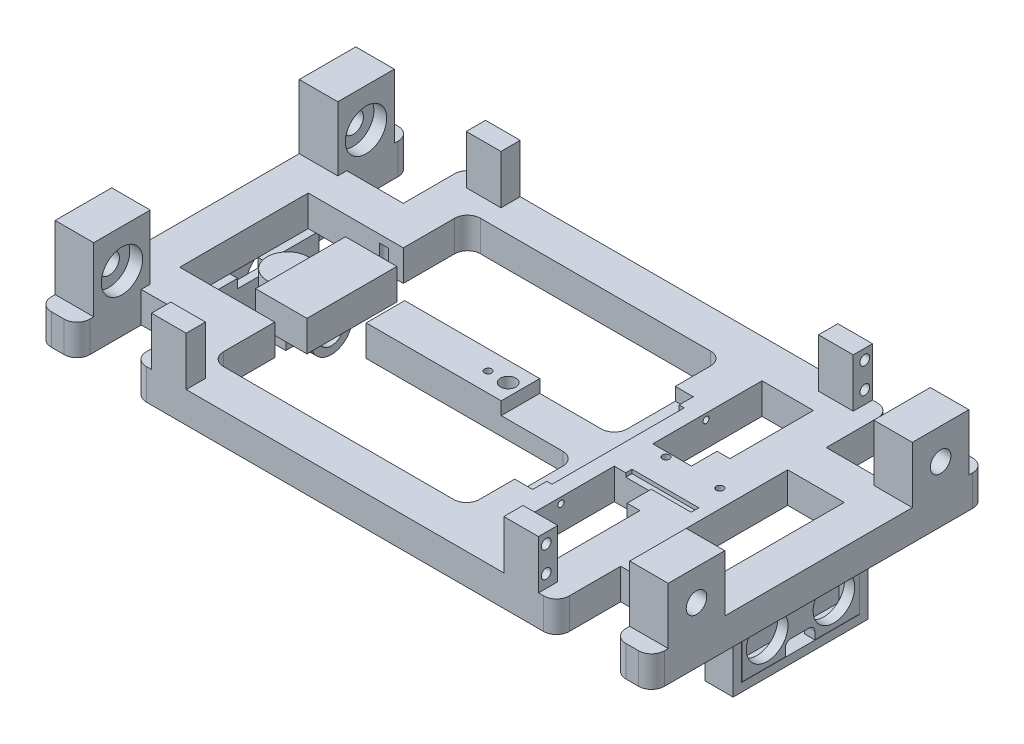
SolidWorks part; units mm, degrees
note: The reader was unsure of these and kept them because the rebuilt part matched: shared geometry of "Sketch42<4>", "Sketch103<3>".
other "DogBody"
other "frontCover"
ref_plane "Front Plane" through (0, 0, 0) normal (0, 0, 1) x (1, 0, 0)
ref_plane "Top Plane" through (0, 0, 0) normal (0, 1, 0) x (1, 0, 0)
ref_plane "Right Plane" through (0, 0, 0) normal (1, 0, 0) x (0, 0, -1)
sketch "Sketch1" plane through (0, 0, 0) normal (0, 1, 0) x (1, 0, 0)
  line L0 (-104.3, -65) -> (-104.3, -7.5)
  line L1 (-119.3, -65) -> (-104.3, -65)
  line L2 (-119.3, -65) -> (-119.3, 65)
  line L3 (-119.3, 65) -> (-104.3, 65)
  line L4 (119.3, -65) -> (119.3, 65)
  line L5 (104.3, 65) -> (104.3, 7.5)
  line L6 (-82.3, -65) -> (-82.3, -7.5)
  line L7 (-67.3, -50) -> (-67.3, -17.5)
  line L8 (82.3, -65) -> (82.3, -7.5)
  line L9 (67.3, -50) -> (67.3, -17.5)
  line L10 (-119.3, 0) -> (119.3, 0) construction
  line L11 (-104.3, -7.5) -> (-82.3, -7.5)
  line L12 (-104.3, 7.5) -> (-82.3, 7.5)
  line L13 (-63.3, -7.5) -> (-63.3, -17.5)
  line L14 (-67.3, 17.5) -> (-63.3, 17.5)
  line L15 (-67.3, 50) -> (67.3, 50)
  line L16 (-82.3, 65) -> (82.3, 65)
  line L18 (104.3, 65) -> (119.3, 65)
  line L19 (104.3, -65) -> (119.3, -65)
  line L20 (-67.3, -17.5) -> (-63.3, -17.5)
  line L21 (-82.3, -65) -> (82.3, -65)
  line L22 (-67.3, -50) -> (67.3, -50)
  line L23 (-104.3, 7.5) -> (-104.3, 65)
  line L24 (-82.3, 7.5) -> (-82.3, 65)
  line L25 (-67.3, 17.5) -> (-67.3, 50)
  line L26 (67.3, 17.5) -> (67.3, 50)
  line L27 (82.3, 7.5) -> (82.3, 65)
  line L28 (104.3, -7.5) -> (104.3, -65)
  line L29 (-119.3, 7.5) -> (119.3, 7.5) construction
  line L30 (-119.3, -7.5) -> (119.3, -7.5) construction
  line L31 (82.3, -7.5) -> (104.3, -7.5)
  line L32 (82.3, 7.5) -> (104.3, 7.5)
  line L33 (-63.3, -7.5) -> (63.3, -7.5)
  line L34 (-63.3, 7.5) -> (63.3, 7.5)
  line L35 (-104.3, 65) -> (-82.3, 65) construction
  line L36 (82.3, 65) -> (104.3, 65) construction
  line L37 (82.3, -65) -> (104.3, -65) construction
  line L38 (-82.3, -65) -> (-104.3, -65) construction
  line L39 (-63.3, 17.5) -> (-63.3, 7.5)
  line L40 (0, -1000) -> (0, 49000) construction
  line L41 (63.3, -7.5) -> (63.3, -17.5)
  line L42 (67.3, -17.5) -> (63.3, -17.5)
  line L43 (67.3, 17.5) -> (63.3, 17.5)
  line L44 (63.3, 17.5) -> (63.3, 7.5)
  dimension "D1" = 65
  dimension "D2" = 130
  dimension "D3" = 15
  dimension "D4" = 22
  dimension "D5" = 15
  dimension "D6" = 15
  dimension "D7" = 22
  dimension "D11" = 15
  dimension "D12" = 15
  dimension "D13" = 238.6
  dimension "D14" = 119.3
  dimension "D15" = 10
  dimension "D16" = 4
  dimension "D17" = 10
  dimension "D9" = 7.5
  dimension "D10" = 7.5
extrude "Boss-Extrude1" add sketch "Sketch1" along normal blind 12
sketch "Sketch2" plane through (0, 12, 0) normal (0, 1, 0) x (1, 0, 0)
  line L0 (-82.3, 65) -> (-82.3, 7.5) construction
  line L1 (-75.3, 57.5) -> (-63.3, 57.5)
  line L2 (-75.3, 57.5) -> (-75.3, 65)
  line L3 (-75.3, 65) -> (-63.3, 65)
  line L4 (-63.3, 57.5) -> (-63.3, 65)
  line L5 (82.3, 65) -> (-82.3, 65) construction
  line L6 (-75.3, 57) -> (-63.3, 57) construction
  line L7 (-112.3144, 32.5) -> (114.0355, 32.5) construction
  line L8 (0, 0) -> (0, 64.2149) construction
  line L14 (0, 0) -> (-63.3, 0) construction
  line L15 (-75.3, -57) -> (-63.3, -57) construction
  line L16 (-75.3, -65) -> (-63.3, -65)
  line L17 (-63.3, -57.5) -> (-63.3, -65)
  line L18 (-75.3, -57.5) -> (-63.3, -57.5)
  line L19 (-75.3, -57.5) -> (-75.3, -65)
  line L22 (-63.3, -7.5) -> (-63.3, 0)
  line L23 (-63.3, 0) -> (-63.3, 7.5)
  line L24 (-75.3, 7.5) -> (-75.3, 0)
  line L25 (-75.3, 0) -> (-75.3, -7.5)
  line L26 (75.3, -57) -> (63.3, -57) construction
  line L27 (75.3, -57.5) -> (75.3, -65)
  line L28 (75.3, -57.5) -> (63.3, -57.5)
  line L29 (63.3, -57.5) -> (63.3, -65)
  line L30 (75.3, -65) -> (63.3, -65)
  line L31 (-75.3, 0) -> (-136.6898, 0) construction
  line L33 (75.3, 7.5) -> (75.3, 0)
  line L35 (63.3, 0) -> (63.3, 7.5)
  line L36 (63.3, -7.5) -> (63.3, 0)
  line L38 (75.3, 0) -> (75.3, -7.5)
  line L39 (75.3, 57) -> (63.3, 57) construction
  line L40 (75.3, 65) -> (63.3, 65)
  line L41 (63.3, 57.5) -> (63.3, 65)
  line L42 (75.3, 57.5) -> (63.3, 57.5)
  line L43 (75.3, 57.5) -> (75.3, 65)
  line L50 (75.3, -7.5) -> (75.3, -17.5)
  line L51 (75.3, -17.5) -> (63.3, -17.5)
  line L52 (63.3, -7.5) -> (63.3, -17.5)
  line L54 (-75.3, 7.5) -> (-75.3, 17.5)
  line L55 (-75.3, 17.5) -> (-63.3, 17.5)
  line L56 (-63.3, 7.5) -> (-63.3, 17.5)
  line L58 (-63.3, -7.5) -> (-63.3, -17.5)
  line L59 (-63.3, -17.5) -> (-75.3, -17.5)
  line L60 (-75.3, -7.5) -> (-75.3, -17.5)
  line L61 (63.3, 7.5) -> (63.3, 17.5)
  line L62 (63.3, 17.5) -> (75.3, 17.5)
  line L63 (75.3, 7.5) -> (75.3, 17.5)
  point P29 (-63.3, 0)
  point P32 (-75.3, 0)
  dimension "D1" = 7
  dimension "D2" = 7.5
  dimension "D3" = 12
  dimension "D4" = 10
  dimension "D5" = 24.5
  dimension "D6" = 10
  dimension "D7" = 10
  dimension "D8" = 10
extrude "Boss-Extrude2" add sketch "Sketch2" along normal blind 19
sketch "Sketch3" plane through (-75.3, 0, 0) normal (-1, 0, 0) x (0, 0, 1)
  line L0 (-37.5, -10.7851) -> (-37.5, 36.9377) construction
  line L1 (-57.5, 31) -> (-57.5, 12) construction
  line L2 (-65, 12) -> (65, 12) construction
  line L3 (0, 0) -> (0, 40.8102) construction
  line L4 (-65, 0) -> (65, 0) construction
  circle A0 centre (-62, 17) radius 1.9
  circle A1 centre (-62, 27) radius 1.9
  circle A2 centre (-13, 17) radius 1.9
  circle A3 centre (-13, 27) radius 1.9
  circle A4 centre (13, 27) radius 1.9
  circle A5 centre (13, 17) radius 1.9
  circle A6 centre (62, 17) radius 1.9
  circle A7 centre (62, 27) radius 1.9
  dimension "D3" = 3.8
  dimension "D4" = 3.8
  dimension "D1" = 4.5
  dimension "D2" = 4.5
  dimension "D5" = 10
  dimension "D6" = 5
  dimension "D7" = 24.5
extrude "Cut-Extrude1" cut sketch "Sketch3" against normal through all
sketch "Sketch4" plane through (104.3, 0, 0) normal (-1, 0, 0) x (0, 0, 1)
  line L0 (57.5, 31) -> (57.5, 12) construction
  line L1 (-65, 12) -> (65, 12) construction
  line L2 (-1000, 0) -> (49000, 0) construction
  line L3 (0, -1000) -> (0, 49000) construction
  line L4 (65, 31) -> (65, 12) construction
  line L5 (-58.5, 12) -> (-36.5, 12)
  line L6 (-58.5, 12) -> (-58.5, 34)
  line L7 (-58.5, 34) -> (-36.5, 34)
  line L8 (-36.5, 12) -> (-36.5, 34)
  line L9 (58.5, 12) -> (36.5, 12)
  line L10 (58.5, 12) -> (58.5, 34)
  line L11 (58.5, 34) -> (36.5, 34)
  line L12 (36.5, 12) -> (36.5, 34)
  line L13 (-65, 31) -> (-65, 12) construction
  circle A0 centre (47.5, 22) radius 8.05
  circle A1 centre (-47.5, 22) radius 8.05
  dimension "D1" = 16.1
  dimension "D2" = 10
  dimension "D3" = 10
  dimension "D4" = 22
  dimension "D5" = 22
  dimension "D6" = 22
  dimension "D7" = 22
  dimension "D8" = 6.5
  dimension "D9" = 6.5
extrude "Boss-Extrude3" add sketch "Sketch4" against normal blind 5 separate body
sketch "Sketch6" plane through (109.3, 0, 0) normal (1, 0, 0) x (0, 0, -1)
  line L5 (-58.5, 12) -> (-36.5, 12)
  line L10 (58.5, 12) -> (36.5, 12)
  line L11 (58.5, 12) -> (58.5, 34)
  line L12 (58.5, 34) -> (36.5, 34)
  line L13 (36.5, 12) -> (36.5, 34)
  line L14 (-58.5, 12) -> (-58.5, 34)
  line L15 (-58.5, 34) -> (-36.5, 34)
  line L16 (-36.5, 12) -> (-36.5, 34)
  circle A0 centre (-47.5, 22) radius 4
  circle A1 centre (47.5, 22) radius 4
  dimension "D1" = 8
  dimension "D2" = 8
extrude "Boss-Extrude4" add sketch "Sketch6" along normal blind 6
mirror "Mirror1" about plane through (0, 0, 0) normal (1, 0, 0) of bodies 228 106 107
sketch "Sketch7" plane through (0, 0, 0) normal (0, 1, 0) x (1, 0, 0)
  line L0 (-104.3, 36.5) -> (-104.3, 58.5) construction
  line L1 (-104.3, 40) -> (-82.3, 40)
  line L2 (-104.3, 40) -> (-104.3, 25)
  line L4 (-82.3, 40) -> (-82.3, 25)
  line L5 (-75.3, 57.5) -> (-63.3, 57.5) construction
  line L7 (-104.3, 25) -> (-82.3, 25)
  line L9 (-1000, 0) -> (49000, 0) construction
  line L10 (0, -1000) -> (0, 49000) construction
  line L11 (104.3, 40) -> (104.3, 25)
  line L12 (104.3, 25) -> (82.3, 25)
  line L13 (82.3, 40) -> (82.3, 25)
  line L14 (104.3, 40) -> (82.3, 40)
  line L15 (104.3, -40) -> (82.3, -40)
  line L16 (82.3, -40) -> (82.3, -25)
  line L17 (104.3, -25) -> (82.3, -25)
  line L18 (104.3, -40) -> (104.3, -25)
  line L19 (-104.3, -40) -> (-104.3, -25)
  line L20 (-104.3, -25) -> (-82.3, -25)
  line L21 (-82.3, -40) -> (-82.3, -25)
  line L22 (-104.3, -40) -> (-82.3, -40)
  dimension "D1" = 17.5
  dimension "D2" = 15
  dimension "D3" = 22
extrude "Boss-Extrude5" add sketch "Sketch7" along normal blind 12
sketch "Sketch8" plane through (0, 12, 0) normal (0, 1, 0) x (1, 0, 0)
  line L1 (-104.3, 25) -> (-82.3, 25)
  line L2 (-104.3, 25) -> (-104.3, -25)
  line L3 (-104.3, -25) -> (-82.3, -25)
  line L4 (-82.3, 25) -> (-82.3, -25)
  line L5 (82.3, -25) -> (104.3, -25)
  line L6 (82.3, -25) -> (82.3, 25)
  line L7 (82.3, 25) -> (104.3, 25)
  line L8 (104.3, -25) -> (104.3, 25)
extrude "Cut-Extrude2" cut sketch "Sketch8" against normal through all
sketch "Sketch14" plane through (0, 0, 0) normal (0, 1, 0) x (1, 0, 0)
  line L0 (-67.3, -50) -> (67.3, -50) construction
  line L1 (-7.5, -50) -> (7.5, -50)
  line L2 (-7.5, -50) -> (-7.5, -7.5)
  line L3 (-7.5, 50) -> (7.5, 50)
  line L4 (7.5, -50) -> (7.5, -7.5)
  line L5 (67.3, 50) -> (-67.3, 50) construction
  line L6 (63.3, -7.5) -> (-63.3, -7.5) construction
  line L7 (-63.3, 7.5) -> (63.3, 7.5) construction
  line L8 (7.5, -7.5) -> (-7.5, -7.5)
  line L9 (-7.5, 7.5) -> (7.5, 7.5)
  line L10 (7.5, 7.5) -> (7.5, 50)
  line L11 (-7.5, 7.5) -> (-7.5, 50)
  dimension "D1" = 15
  dimension "D2" = 7.5
extrude "Boss-Extrude8" add sketch "Sketch14" along normal up to surface (12 mm away) up to face at (0, 12, 0)
sketch "Sketch15" plane through (0, 12, 0) normal (0, 1, 0) x (1, 0, 0)
  line L1 (3.3, -31.25) -> (39.3, -31.25)
  line L2 (3.3, -31.25) -> (3.3, 31.25)
  line L4 (39.3, -31.25) -> (39.3, 31.25)
  line L5 (75.3, 57.5) -> (75.3, 65) construction
  line L8 (3.3, 31.25) -> (39.3, 31.25)
  line L9 (-47.3, 14) -> (0.7, 14)
  line L10 (-47.3, 14) -> (-47.3, -14)
  line L11 (-47.3, -14) -> (0.7, -14)
  line L12 (0.7, 14) -> (0.7, -14)
  line L13 (3.3, 27.75) -> (39.3, 27.75) construction
  line L14 (3.3, -27.75) -> (39.3, -27.75) construction
  line L15 (-75.3, 65) -> (-75.3, 57.5) construction
  line L16 (-39.3, -998.765) -> (-39.3, 49001.235) construction
  line L17 (39.3, -1009.0627) -> (39.3, 48990.9373) construction
  point P17 (-75.3, 61.25)
  dimension "D1" = 36
  dimension "D2" = 36
  dimension "D3" = 48
  dimension "D4" = 28
  dimension "D5" = 31.25
  dimension "D6" = 62.5
  dimension "D7" = 55.5
  dimension "D8" = 3.5
  dimension "D9" = 28
  dimension "D10" = 14
  dimension "D11" = 2.6
sketch "Sketch16" plane through (0, 12, 0) normal (0, 1, 0) x (1, 0, 0)
  line L1 (-7.5, 50) -> (7.5, 50)
  line L2 (-7.5, 50) -> (-7.5, 7.5)
  line L3 (-7.5, 7.5) -> (7.5, 7.5)
  line L4 (7.5, 50) -> (7.5, 7.5)
  line L5 (-7.5, -7.5) -> (7.5, -7.5)
  line L6 (-7.5, -7.5) -> (-7.5, -50)
  line L7 (-7.5, -50) -> (7.5, -50)
  line L8 (7.5, -7.5) -> (7.5, -50)
extrude "Cut-Extrude8" cut sketch "Sketch16" against normal through all
sketch "Sketch17" plane through (0, 0, 0) normal (0, 1, 0) x (1, 0, 0)
  line L0 (67.3, 50) -> (-67.3, 50) construction
  line L1 (32.3, 50) -> (47.3, 50)
  line L2 (32.3, 50) -> (32.3, 7.5)
  line L3 (32.3, 7.5) -> (47.3, 7.5)
  line L4 (47.3, 50) -> (47.3, 7.5)
  line L5 (-63.3, 7.5) -> (63.3, 7.5) construction
  line L6 (63.3, -7.5) -> (-63.3, -7.5) construction
  line L7 (32.3, -7.5) -> (47.3, -7.5)
  line L8 (32.3, -7.5) -> (32.3, -50)
  line L9 (32.3, -50) -> (47.3, -50)
  line L10 (47.3, -7.5) -> (47.3, -50)
  line L11 (-67.3, -50) -> (67.3, -50) construction
  line L12 (39.3, -201009.0627) -> (39.3, 248990.9373) construction
  dimension "D1" = 15
  dimension "D2" = 15
  dimension "D3" = 7
  dimension "D4" = 7
extrude "Boss-Extrude9" add sketch "Sketch17" along normal up to surface (12 mm away) up to face at (-93.3, 12, 0)
extrude "Cut-Extrude9" cut sketch "Sketch15" against normal blind 5 contours L8 L2 L1 L4
sketch "Sketch18" plane through (39.3, 0, 0) normal (-1, 0, 0) x (0, 0, 1)
  line L0 (31.25, 7) -> (-31.25, 7) construction
  line L1 (-31.25, 12) -> (-31.25, 7) construction
  line L2 (31.25, 12) -> (31.25, 7) construction
  circle A0 centre (28.25, 9.7) radius 1.2
  circle A1 centre (-28.25, 9.7) radius 1.2
  dimension "D1" = 2.4
  dimension "D2" = 2.4
  dimension "D3" = 2.7
  dimension "D4" = 2.7
  dimension "D5" = 3
  dimension "D6" = 3
extrude "Cut-Extrude10" cut sketch "Sketch18" against normal up to next
sketch "Sketch19" plane through (39.3, 0, 0) normal (-1, 0, 0) x (0, 0, 1)
  line L0 (-31.25, 7) -> (-7.5, 7) construction
  line L1 (-25.75, 7) -> (25.75, 7)
  line L2 (-25.75, 7) -> (-25.75, 14)
  line L3 (-25.75, 14) -> (25.75, 14)
  line L4 (25.75, 7) -> (25.75, 14)
  dimension "D1" = 7
  dimension "D2" = 51.5
  dimension "D3" = 25.75
extrude "Cut-Extrude11" cut sketch "Sketch19" against normal blind 2
sketch "Sketch41" plane through (0, 0, 0) normal (0, -1, 0) x (1, 0, 0)
  line L5 (119.3, 65) -> (119.3, -65) construction
  line L8 (104.3, 22.75) -> (104.3, -22.75) construction
  line L24 (104.3, -22.75) -> (101.3, -22.75)
  line L25 (104.3, -22.75) -> (104.3, 22.75)
  line L26 (104.3, 22.75) -> (101.3, 22.75)
  line L27 (101.3, -22.75) -> (101.3, 22.75)
  line L28 (101.3, 22.75) -> (104.3, 22.75)
  line L29 (101.3, 22.75) -> (101.3, 26.25)
  line L30 (101.3, 26.25) -> (104.3, 26.25)
  line L31 (104.3, 22.75) -> (104.3, 26.25)
  line L32 (101.3, -22.75) -> (104.3, -22.75)
  line L33 (101.3, -22.75) -> (101.3, -26.25)
  line L34 (101.3, -26.25) -> (104.3, -26.25)
  line L35 (104.3, -22.75) -> (104.3, -26.25)
  dimension "D1" = 15
  dimension "D7" = 3.5
  dimension "D8" = 3.5
  dimension "D9" = 3
extrude "Boss-Extrude18" add sketch "Sketch41" along normal blind 24 separate body
sketch "Sketch42" plane through (104.3, 0, 0) normal (1, 0, 0) x (0, 0, -1)
  line L1 (-26.25, 0) -> (26.25, 0)
  line L2 (-26.25, 0) -> (-26.25, -24)
  line L3 (-26.25, -24) -> (26.25, -24)
  line L4 (26.25, 0) -> (26.25, -24)
  line L5 (-22.95, 0) -> (22.95, 0)
  line L6 (-22.95, 0) -> (-22.95, -20.7)
  line L7 (-22.95, -20.7) -> (22.95, -20.7)
  line L8 (22.95, 0) -> (22.95, -20.7)
  line L9 (-5.5, -5.0608) -> (5.5, -5.0608) construction
  line L10 (-5.5, -5.0608) -> (-5.5, 3.3558) construction
  line L11 (-5.5, 3.3558) -> (5.5, 3.3558) construction
  line L12 (5.5, -5.0608) -> (5.5, 3.3558) construction
  line L13 (-5.5, -3.3) -> (-19.95, -3.3)
  line L14 (-5.5, -3.3) -> (-5.5, 0)
  line L15 (-5.5, 0) -> (-19.95, 0)
  line L16 (-19.95, -3.3) -> (-19.95, 0)
  line L17 (5.5, -3.3) -> (19.95, -3.3)
  line L18 (5.5, -3.3) -> (5.5, 0)
  line L19 (5.5, 0) -> (19.95, 0)
  line L20 (19.95, -3.3) -> (19.95, 0)
  line L21 (5.5, -3.5) -> (-5.5, -3.5)
  line L22 (5.5, -3.5) -> (5.5, 0)
  line L23 (5.5, 0) -> (-5.5, 0)
  line L24 (-5.5, -3.5) -> (-5.5, 0)
  line M8 (26.25, 0) -> (-26.25, 0)
  line M9 (-26.25, 0) -> (-26.25, -24)
  line M10 (-26.25, -24) -> (26.25, -24)
  line M11 (26.25, -24) -> (26.25, 0)
  dimension "D1" = 3.3
  dimension "D2" = 3.3
  dimension "D3" = 3.3
  dimension "D4" = 11
  dimension "D5" = 5.5
  dimension "D6" = 3.3
  dimension "D7" = 3.3
  dimension "D8" = 3
  dimension "D9" = 3
  dimension "D10" = 3.5
extrude "Boss-Extrude19" add sketch "Sketch42" along normal blind 8 contours L8 L7 L6 M8 M9 M10 M11
sketch "Sketch48" plane through (104.3, 0, 0) normal (1, 0, 0) x (0, 0, -1)
  line L0 (-13, -10.5) -> (13, -10.5) construction
  line L1 (-5.25, -2.5) -> (-5.25, -0.1)
  line L2 (-22.95, -20.7) -> (22.95, -20.7) construction
  line L3 (-5.95, -17.7) -> (-5.95, -20.6)
  line L4 (-3.75, -17.7) -> (3.35, -17.7) construction
  line L5 (-3.75, -15.5) -> (3.35, -15.5)
  line L7 (5.55, -17.7) -> (5.55, -20.6)
  line L8 (-22.95, -20.7) -> (22.95, -20.7) construction
  line L9 (-3.75, -2.5) -> (3.7505, -2.5) construction
  line L11 (-3.75, -4) -> (3.7505, -4)
  line L12 (-65, 0) -> (65, 0) construction
  line L13 (-22.95, 0) -> (-22.95, -20.7) construction
  line L14 (-22.85, -20.6) -> (-5.95, -20.6)
  line L15 (-22.85, -20.6) -> (-22.85, -0.1)
  line L16 (-22.85, -0.1) -> (-5.25, -0.1)
  line L17 (22.85, -20.6) -> (22.85, -0.1)
  line L18 (22.95, 0) -> (22.95, -20.7) construction
  line L19 (5.55, -20.6) -> (22.85, -20.6)
  line L20 (5.25, -2.4627) -> (5.25, -0.1)
  line L21 (5.25, -0.1) -> (22.85, -0.1)
  circle A0 centre (-13, -10.5) radius 8.1
  circle A1 centre (13, -10.5) radius 8.1
  arc A2 (-3.75, -15.5) -> (-5.95, -17.7) centre (-3.75, -17.7) ccw
  arc A3 (5.55, -17.7) -> (3.35, -15.5) centre (3.35, -17.7) ccw
  arc A5 (-5.25, -2.5) -> (-3.75, -4) centre (-3.75, -2.5) ccw
  arc A6 (3.7505, -4) -> (5.25, -2.4627) centre (3.7505, -2.5) ccw
  point P13 (0, -17.7)
  point P23 (0, -2.5)
  dimension "D1" = 16.2
  dimension "D2" = 16.2
  dimension "D6" = 2.2
  dimension "D7" = 11.5
  dimension "D10" = 1.5
  dimension "D12" = 5.25
  dimension "D8" = 2.2
  dimension "D11" = 1.5
  dimension "D19" = 5.1
  dimension "D22" = 5.55
  dimension "D3" = 26
  dimension "D4" = 13
  dimension "D5" = 10.2
  dimension "D9" = 10.5
  dimension "D13" = 3.9
  dimension "D14" = 0.1
  dimension "D15" = 0.1
  dimension "D16" = 0.1
  dimension "D17" = 0.1
  dimension "D18" = 7.5005
  dimension "D20" = 2.4
  dimension "D21" = 2.9
extrude "Boss-Extrude22" add sketch "Sketch48" along normal blind 4 from offset 5 separate body
sketch "Sketch55" plane through (0, 12, 0) normal (0, 1, 0) x (1, 0, 0)
  line L0 (63.3, 65) -> (-63.3, 65) construction
  line L1 (-63.3, 57.5) -> (-61.8, 57.5)
  line L2 (-63.3, 57.5) -> (-63.3, 65)
  line L3 (-63.3, 65) -> (-61.8, 65)
  line L4 (-61.8, 57.5) -> (-61.8, 65)
  line L6 (63.3, 57.5) -> (61.8, 57.5)
  line L7 (63.3, 57.5) -> (63.3, 65)
  line L8 (63.3, 65) -> (61.8, 65)
  line L9 (61.8, 57.5) -> (61.8, 65)
  line L19 (-63.3, -65) -> (63.3, -65) construction
  line L20 (63.3, -57.5) -> (61.8, -57.5)
  line L21 (63.3, -57.5) -> (63.3, -65)
  line L22 (63.3, -65) -> (61.8, -65)
  line L23 (61.8, -57.5) -> (61.8, -65)
  line L25 (-63.3, -57.5) -> (-61.8, -57.5)
  line L26 (-63.3, -57.5) -> (-63.3, -65)
  line L27 (-63.3, -65) -> (-61.8, -65)
  line L28 (-61.8, -57.5) -> (-61.8, -65)
  dimension "D2" = 1.5
  dimension "D3" = 1.5
  dimension "D5" = 1.5
  dimension "D6" = 1.5
extrude "Boss-Extrude27" add sketch "Sketch55" along normal up to surface (19 mm away) up to face at (-69.3, 31, 0)
extrude "Cut-Extrude27" cut sketch "Sketch42<4>" against normal up to next (3 mm away) contours L24 L21 L22 L18 L5 L14
sketch "Sketch42<4>" plane through (104.3, 0, 0) normal (1, 0, 0) x (0, 0, -1) same geometry as "Sketch42"
move or copy body "Body-Move/Copy1" bodies to move or copy 172 copy no translate (-1, 0, 0) parameters "D1"=1, "D2"=0, "D3"=0
sketch "Sketch60" plane through (0, 34, 0) normal (0, 1, 0) x (1, 0, 0)
  line L0 (-104.3, 36.5) -> (-104.3, 58.5) construction
  line L1 (-104.3, 58.5) -> (-115.3, 58.5) construction
  line L2 (-115.3, 58.5) -> (-115.3, 36.5) construction
  line L3 (-115.3, 36.5) -> (-104.3, 36.5) construction
  line L4 (-104.3, -58.5) -> (-104.3, -36.5) construction
  line L5 (-104.3, -36.5) -> (-115.3, -36.5) construction
  line L7 (-115.3, -58.5) -> (-104.3, -58.5) construction
  line L8 (-104.3, 36.5) -> (-104.3, 58.5)
  line L9 (-104.3, 58.5) -> (-115.3, 58.5)
  line L10 (-115.3, 58.5) -> (-115.3, 36.5)
  line L11 (-115.3, 36.5) -> (-104.3, 36.5)
  line L12 (-104.3, -58.5) -> (-104.3, -36.5)
  line L13 (-104.3, -36.5) -> (-115.3, -36.5)
  line L14 (-115.3, -36.5) -> (-115.3, -58.5)
  line L15 (-115.3, -58.5) -> (-104.3, -58.5)
extrude "Boss-Extrude28" add sketch "Sketch60" along normal blind 3
sketch "Sketch62" plane through (0, 0, 0) normal (0, -1, 0) x (1, 0, 0)
  line L0 (0, -1000) -> (0, 49000) construction
  line L2 (-67.3, 17.5) -> (-67.3, 50) construction
  line L4 (-67.3, -50) -> (-67.3, -17.5) construction
  line L6 (82.3, -65) -> (-82.3, -65) construction
  line L7 (-82.3, 65) -> (82.3, 65) construction
  line L8 (32.3, -50) -> (-67.3, -50) construction
  circle A0 centre (-74.8, 25) radius 1.825
  circle A1 centre (-74.8, -25) radius 1.825
  circle A2 centre (-74.8, -57.5) radius 1.825
  circle A3 centre (-74.8, 57.5) radius 1.825
  circle A4 centre (0, 57.5) radius 1.825
  circle A5 centre (0, -57.5) radius 1.825
  circle A6 centre (74.8, -57.5) radius 1.825
  circle A7 centre (74.8, -25) radius 1.825
  circle A8 centre (74.8, 25) radius 1.825
  circle A9 centre (74.8, 57.5) radius 1.825
  dimension "D3" = 3.65
  dimension "D4" = 3.65
  dimension "D9" = 3.65
  dimension "D10" = 3.65
  dimension "D12" = 7.5
  dimension "D14" = 3.65
  dimension "D15" = 3.65
  dimension "D1" = 25
  dimension "D2" = 25
  dimension "D5" = 7.5
  dimension "D6" = 7.5
  dimension "D7" = 7.5
  dimension "D8" = 7.5
  dimension "D11" = 7.5
  dimension "D13" = 7.5
  dimension "D16" = 7.5
extrude "Cut-Extrude33" cut sketch "Sketch62" against normal blind 9
fillet "Fillet4" radius 5 18 edges at (-119.3, 6, -65) (-104.3, 6, -65) (-82.3, 6, -65) (-119.3, 6, 65) (-104.3, 6, 65) (-82.3, 6, 65) (119.3, 6, -65) (104.3, 6, -65) (82.3, 6, -65) (119.3, 6, 65) (104.3, 6, 65) (82.3, 6, 65) (32.3, 3.5, -7.5) (-67.3, 6, 50) (32.3, 6, 50) (32.3, 3.5, 7.5) (-67.3, 6, -50) (32.3, 6, -50) tangent propagation no
sketch "Sketch65" plane through (115.3, 0, 0) normal (1, 0, 0) x (0, 0, -1)
  line L4 (-58.5, 34) -> (-58.5, 12)
  line L5 (-58.5, 12) -> (-36.5, 12)
  line L6 (-36.5, 12) -> (-36.5, 34)
  line L7 (-36.5, 34) -> (-58.5, 34)
  line L8 (-58.5, 34) -> (-58.5, 12)
  line L9 (-58.5, 12) -> (-36.5, 12)
  line L10 (-36.5, 12) -> (-36.5, 34)
  line L11 (-36.5, 34) -> (-58.5, 34)
  line L12 (58.5, 12) -> (58.5, 34)
  line L13 (58.5, 34) -> (36.5, 34)
  line L14 (36.5, 34) -> (36.5, 12)
  line L15 (36.5, 12) -> (58.5, 12)
  line L16 (58.5, 12) -> (58.5, 34)
  line L17 (58.5, 34) -> (36.5, 34)
  line L18 (36.5, 34) -> (36.5, 12)
  line L19 (36.5, 12) -> (58.5, 12)
  circle A0 centre (-47.5, 22) radius 4 construction
  circle A1 centre (-47.5, 22) radius 4
  circle A2 centre (47.5, 22) radius 4 construction
  circle A3 centre (47.5, 22) radius 4
  dimension "D1" = 0
  dimension "D2" = 0
extrude "Boss-Extrude29" add sketch "Sketch65" along normal up to surface (4 mm away) up to face at (119.3, 6, 0)
sketch "Sketch66" plane through (-115.3, 0, 0) normal (-1, 0, 0) x (0, 0, 1)
  line L4 (-58.5, 37) -> (-58.5, 12)
  line L5 (-58.5, 12) -> (-36.5, 12)
  line L6 (-36.5, 12) -> (-36.5, 37)
  line L7 (-36.5, 37) -> (-58.5, 37)
  line L8 (-58.5, 37) -> (-58.5, 12)
  line L9 (-58.5, 12) -> (-36.5, 12)
  line L10 (-36.5, 12) -> (-36.5, 37)
  line L11 (-36.5, 37) -> (-58.5, 37)
  line L12 (58.5, 12) -> (58.5, 37)
  line L13 (58.5, 37) -> (36.5, 37)
  line L14 (36.5, 37) -> (36.5, 12)
  line L15 (36.5, 12) -> (58.5, 12)
  line L16 (58.5, 12) -> (58.5, 37)
  line L17 (58.5, 37) -> (36.5, 37)
  line L18 (36.5, 37) -> (36.5, 12)
  line L19 (36.5, 12) -> (58.5, 12)
  circle A0 centre (-47.5, 22) radius 4 construction
  circle A1 centre (-47.5, 22) radius 4
  circle A2 centre (47.5, 22) radius 4 construction
  circle A3 centre (47.5, 22) radius 4
  dimension "D1" = 0
  dimension "D2" = 0
extrude "Boss-Extrude30" add sketch "Sketch66" along normal up to surface (4 mm away) up to face at (-119.3, 6, 0)
sketch "Sketch68" plane through (-63.3, 0, 0) normal (1, 0, 0) x (0, 0, -1)
  line L8 (-17.5, 0) -> (-7.5, 0)
  line L9 (-7.5, 0) -> (-7.5, 12)
  line L10 (-7.5, 12) -> (7.5, 12)
  line L11 (7.5, 12) -> (7.5, 0)
  line L12 (7.5, 0) -> (17.5, 0)
  line L13 (17.5, 0) -> (17.5, 31)
  line L14 (17.5, 31) -> (-17.5, 31)
  line L15 (-17.5, 31) -> (-17.5, 0)
  line L16 (-17.5, 0) -> (-7.5, 0)
  line L17 (-7.5, 0) -> (-7.5, 12)
  line L18 (-7.5, 12) -> (7.5, 12)
  line L19 (7.5, 12) -> (7.5, 0)
  line L20 (7.5, 0) -> (17.5, 0)
  line L21 (17.5, 0) -> (17.5, 31)
  line L22 (17.5, 31) -> (-17.5, 31)
  line L23 (-17.5, 31) -> (-17.5, 0)
  dimension "D1" = 0
extrude "Boss-Extrude32" add sketch "Sketch68" along normal blind 1
sketch "Sketch69" plane through (63.3, 0, 0) normal (-1, 0, 0) x (0, 0, 1)
  line L8 (7.5, 0) -> (17.5, 0)
  line L9 (17.5, 0) -> (17.5, 31)
  line L10 (17.5, 31) -> (-17.5, 31)
  line L11 (-17.5, 31) -> (-17.5, 0)
  line L12 (-17.5, 0) -> (-7.5, 0)
  line L13 (-7.5, 0) -> (-7.5, 12)
  line L14 (-7.5, 12) -> (7.5, 12)
  line L15 (7.5, 12) -> (7.5, 0)
  line L16 (7.5, 0) -> (17.5, 0)
  line L17 (17.5, 0) -> (17.5, 31)
  line L18 (17.5, 31) -> (-17.5, 31)
  line L19 (-17.5, 31) -> (-17.5, 0)
  line L20 (-17.5, 0) -> (-7.5, 0)
  line L21 (-7.5, 0) -> (-7.5, 12)
  line L22 (-7.5, 12) -> (7.5, 12)
  line L23 (7.5, 12) -> (7.5, 0)
  dimension "D1" = 0
extrude "Boss-Extrude33" add sketch "Sketch69" along normal blind 1
sketch "Sketch67" plane through (0, 12, 0) normal (0, 1, 0) x (1, 0, 0)
  line L5 (-62.3, 7.5) -> (3.3, 7.5) construction
  line L6 (-62.3, -7.5) -> (-6.3, -7.5)
  line L7 (-62.3, -7.5) -> (-62.3, 7.5)
  line L8 (-62.3, 7.5) -> (-6.3, 7.5)
  line L9 (-6.3, -7.5) -> (-6.3, 7.5)
  dimension "D1" = 56
extrude "Boss-Extrude34" add sketch "Sketch67" along normal blind 11
sketch "Sketch70" plane through (-75.3, 0, 0) normal (-1, 0, 0) x (0, 0, 1)
  line L0 (-17.5, 31) -> (17.5, 31) construction
  line L1 (-14.5, 31) -> (14.5, 31) construction
  line L2 (-14.5, 31) -> (-14.5, 23) construction
  line L3 (-14.5, 23) -> (14.5, 23) construction
  line L4 (14.5, 31) -> (14.5, 23) construction
  line L6 (-6, 31) -> (6, 31)
  line L7 (-6, 31) -> (-6, 23)
  line L8 (-6, 23) -> (6, 23)
  line L9 (6, 31) -> (6, 23)
  dimension "D1" = 14.5
  dimension "D2" = 29
  dimension "D3" = 8
  dimension "D4" = 6
  dimension "D5" = 12
extrude "Cut-Extrude35" cut sketch "Sketch70" against normal up to next
sketch "Sketch71" plane through (0, 31, 0) normal (0, 1, 0) x (1, 0, 0)
  line L1 (56.3, -8.1) -> (82.3, -8.1)
  line L2 (56.3, -8.1) -> (56.3, 8.1)
  line L3 (56.3, 8.1) -> (82.3, 8.1)
  line L4 (82.3, -8.1) -> (82.3, 8.1)
  line L7 (82.3, -25) -> (82.3, 25) construction
  dimension "D1" = 16.2
  dimension "D2" = 8.1
  dimension "D3" = 26
extrude "Cut-Extrude36" cut sketch "Sketch71" against normal up to surface (19 mm away) up to face at (-6.04, 12, 0)
sketch "Sketch72" plane through (0, 12, 0) normal (0, 1, 0) x (1, 0, 0)
  line L6 (82.3, -25) -> (82.3, 25) construction
  line L7 (77.8, -8.1) -> (77.8, -5.1)
  line L8 (77.8, -8.1) -> (51.8, -8.1)
  line L10 (77.8, -5.1) -> (51.8, -5.1)
  line L11 (51.8, -8.1) -> (51.8, -5.1)
  dimension "D1" = 3
  dimension "D2" = 26
  dimension "D3" = 30.5
extrude "Cut-Extrude37" cut sketch "Sketch72" against normal blind 1.5
sketch "Sketch73" plane through (0, 12, 0) normal (0, 1, 0) x (1, 0, 0)
  line L0 (75.3, 8.1) -> (62.3, 8.1) construction
  line L1 (82.3, -25) -> (82.3, 25) construction
  circle A0 centre (54.3, 5.6) radius 1.4
  circle A1 centre (75.3, 5.6) radius 1.4
  dimension "D2" = 2.8
  dimension "D3" = 2.8
  dimension "D1" = 21
  dimension "D4" = 2.5
  dimension "D5" = 7
extrude "Cut-Extrude38" cut sketch "Sketch73" against normal blind 10
sketch "Sketch74" plane through (0, 23, 0) normal (0, 1, 0) x (1, 0, 0)
  line L1 (-6.3, 4.5) -> (-12.3, 4.5)
  line L2 (-6.3, 4.5) -> (-6.3, -4.5)
  line L3 (-6.3, -4.5) -> (-12.3, -4.5)
  line L4 (-12.3, 4.5) -> (-12.3, -4.5)
  line L5 (-6.3, -7.5) -> (-6.3, 7.5) construction
  dimension "D1" = 6
  dimension "D2" = 4.5
  dimension "D3" = 4.5
extrude "Boss-Extrude35" add sketch "Sketch74" along normal blind 2.5
sketch "Sketch75" plane through (0, 23, 0) normal (0, 1, 0) x (1, 0, 0)
  line L1 (-12.3, 4.5) -> (-6.3, 4.5)
  line L2 (-12.3, 4.5) -> (-12.3, 7.5)
  line L3 (-12.3, 7.5) -> (-6.3, 7.5)
  line L4 (-6.3, 4.5) -> (-6.3, 7.5)
  line L5 (-12.3, -4.5) -> (-6.3, -4.5)
  line L6 (-12.3, -4.5) -> (-12.3, -7.5)
  line L7 (-12.3, -7.5) -> (-6.3, -7.5)
  line L8 (-6.3, -4.5) -> (-6.3, -7.5)
extrude "Boss-Extrude36" add sketch "Sketch75" along normal blind 2.5 separate body
sketch "Sketch76" plane through (0, 25.5, 0) normal (0, 1, 0) x (1, 0, 0)
  line L0 (-12.3, 4.5) -> (-12.3, -4.5) construction
  line L1 (-12.3, -7.85) -> (-30.8, -7.85) construction
  line L2 (-12.3, -7.85) -> (-12.3, 7.85) construction
  line L3 (-12.3, 7.85) -> (-30.8, 7.85) construction
  line L4 (-30.8, -7.85) -> (-30.8, 7.85) construction
  line L5 (-6.3, -7.5) -> (-6.3, 7.5) construction
  line L6 (-12.3, -7.85) -> (-6.3, -7.85)
  line L7 (-12.3, -7.85) -> (-12.3, 7.85)
  line L8 (-12.3, 7.85) -> (-6.3, 7.85)
  line L9 (-6.3, -7.85) -> (-6.3, 7.85)
  line L10 (-20.475, -1.075) -> (-12.3, -1.075) construction
  line L11 (-30.8, 7.85) -> (-6.3, 7.85)
  line L12 (-30.8, 7.85) -> (-30.8, 10)
  line L13 (-30.8, 10) -> (-6.3, 10)
  line L14 (-6.3, 7.85) -> (-6.3, 10)
  line L15 (-30.8, 10) -> (-32.95, 10)
  line L16 (-30.8, 10) -> (-30.8, -7.85)
  line L17 (-30.8, -7.85) -> (-32.95, -7.85)
  line L18 (-32.95, 10) -> (-32.95, -7.85)
  line L19 (-32.95, -7.85) -> (-6.3, -7.85)
  line L20 (-32.95, -7.85) -> (-32.95, -10)
  line L21 (-32.95, -10) -> (-6.3, -10)
  line L22 (-6.3, -7.85) -> (-6.3, -10)
  line L27 (-22.625, -7.85) -> (-20.475, -7.85) construction
  line L28 (-22.625, -7.85) -> (-22.625, -1.075) construction
  line L29 (-22.625, 7.85) -> (-20.475, 7.85) construction
  line L30 (-20.475, -7.85) -> (-20.475, -1.075) construction
  line L31 (-30.8, -1.075) -> (-22.625, -1.075) construction
  line L32 (-30.8, -1.075) -> (-30.8, 1.075) construction
  line L33 (-30.8, 1.075) -> (-22.625, 1.075) construction
  line L34 (-12.3, -1.075) -> (-12.3, 1.075) construction
  line L35 (-20.475, 1.075) -> (-12.3, 1.075) construction
  line L36 (-22.625, 1.075) -> (-22.625, 7.85) construction
  line L37 (-20.475, 1.075) -> (-20.475, 7.85) construction
  line M25 (-12.3, -4.5) -> (-12.3, -7.5)
  line M26 (-12.3, -7.5) -> (-6.3, -7.5)
  line M27 (-6.3, -7.5) -> (-6.3, -4.5)
  line M28 (-6.3, -4.5) -> (-12.3, -4.5)
  dimension "D1" = 15.7
  dimension "D2" = 7.85
  dimension "D3" = 18.5
  dimension "D4" = 2.15
  dimension "D5" = 2.15
  dimension "D6" = 2.15
  dimension "D7" = 2.15
  dimension "D8" = 2.15
  dimension "D9" = 8.175
  dimension "D10" = 6.775
extrude "Boss-Extrude37" add sketch "Sketch76" along normal blind 2.7 contours L15 L18 L17 L16 L12 | L8 L14 L13 L12 L11 | L9 L8 L7 M28 | L22 L6 L19 L17 L20 L21 | L6 L9 L7 M26 | M28 M25 M26 M27
sketch "Sketch77" plane through (-6.3, 0, 0) normal (1, 0, 0) x (0, 0, -1)
  line L0 (-10, 25.5) -> (-7.5, 23)
  line L1 (-7.5, 23) -> (-7.5, 25.5)
  line L2 (-7.5, 25.5) -> (-10, 25.5)
  line L3 (7.5, 23) -> (7.5, 25.5)
  line L4 (7.5, 25.5) -> (10, 25.5)
  line L5 (10, 25.5) -> (7.5, 23)
extrude "Boss-Extrude38" add sketch "Sketch77" against normal blind 6
sketch "Sketch78" plane through (-6.3, 0, 0) normal (1, 0, 0) x (0, 0, -1)
  line L0 (-10, 28.2) -> (10, 28.2) construction
  line L1 (-7.85, 28.2) -> (-5.85, 28.2)
  line L2 (-7.85, 28.2) -> (-7.85, 26.2)
  line L3 (-7.85, 26.2) -> (-5.85, 26.2)
  line L4 (-5.85, 28.2) -> (-5.85, 26.2)
  line L5 (-10, 28.2) -> (-10, 25.5) construction
  dimension "D1" = 2
  dimension "D2" = 2.15
  dimension "D3" = 2
extrude "Cut-Extrude39" cut sketch "Sketch78" against normal up to next (6 mm away)
sketch "Sketch79" plane through (0, 28.2, 0) normal (0, 1, 0) x (1, 0, 0)
  line L10 (-12.3, -5.85) -> (-12.3, -7.85) construction
  line L37 (-17.3, 7.85) -> (-17.3, -7.85)
  line L39 (-12.3, -5.85) -> (-12.3, -7.85)
  line L40 (-17.3, -7.85) -> (-30.8, -7.85)
  line L41 (-6.3, -10) -> (-6.3, -7.85)
  line L42 (-6.3, -7.85) -> (-30.8, -7.85)
  line L43 (-30.8, -7.85) -> (-30.8, 7.85)
  line L44 (-30.8, 7.85) -> (-12.3, 7.85)
  line L45 (-12.3, 7.85) -> (-12.3, -5.85)
  line L46 (-12.3, -5.85) -> (-6.3, -5.85)
  line L47 (-6.3, -5.85) -> (-6.3, 10)
  line L48 (-6.3, 10) -> (-32.95, 10)
  line L49 (-32.95, 10) -> (-32.95, -10)
  line L50 (-32.95, -10) -> (-6.3, -10)
  line L51 (-6.3, -10) -> (-6.3, -7.85)
  line L52 (-6.3, -7.85) -> (-12.3, -7.85)
  line L53 (-30.8, -7.85) -> (-30.8, 7.85)
  line L54 (-30.8, 7.85) -> (-17.3, 7.85)
  line L56 (-12.3, -5.85) -> (-6.3, -5.85)
  line L57 (-6.3, -5.85) -> (-6.3, 10)
  line L58 (-6.3, 10) -> (-32.95, 10)
  line L59 (-32.95, 10) -> (-32.95, -10)
  line L60 (-32.95, -10) -> (-6.3, -10)
  dimension "D2" = 5
  dimension "D1" = 0
extrude "Boss-Extrude39" add sketch "Sketch79" along normal blind 3
sketch "Sketch80" plane through (0, 31.2, 0) normal (0, 1, 0) x (1, 0, 0)
  line L0 (-6.3, -5.85) -> (-6.3, 10) construction
  circle A0 centre (-9.3, 0) radius 2.75
  dimension "D2" = 5.5
  dimension "D1" = 3
extrude "Cut-Extrude40" cut sketch "Sketch80" against normal blind 3
sketch "Sketch81" plane through (0, 28.2, 0) normal (0, 1, 0) x (1, 0, 0)
  circle A0 centre (-9.3, 0) radius 1.4
  dimension "D1" = 2.8
extrude "Cut-Extrude41" cut sketch "Sketch81" against normal blind 20
sketch "Sketch82" plane through (0, 23, 0) normal (0, 1, 0) x (1, 0, 0)
  line L1 (-12.3, 4.5) -> (-6.3, 4.5)
  line L2 (-12.3, 4.5) -> (-12.3, 7.5)
  line L3 (-12.3, 7.5) -> (-6.3, 7.5)
  line L4 (-6.3, 4.5) -> (-6.3, 7.5)
  line L5 (-12.3, -4.5) -> (-6.3, -4.5)
  line L6 (-12.3, -4.5) -> (-12.3, -7.5)
  line L7 (-12.3, -7.5) -> (-6.3, -7.5)
  line L8 (-6.3, -4.5) -> (-6.3, -7.5)
extrude "Cut-Extrude42" cut sketch "Sketch82" against normal blind 5
sketch "Sketch83" plane through (0, 23, 0) normal (0, -1, 0) x (1, 0, 0)
  line L4 (-12.3, 7.5) -> (-12.3, 4.5)
  line L5 (-12.3, 4.5) -> (-6.3, 4.5)
  line L6 (-6.3, 4.5) -> (-6.3, 7.5)
  line L7 (-6.3, 7.5) -> (-12.3, 7.5)
  line L8 (-12.3, 7.5) -> (-12.3, 4.5)
  line L9 (-12.3, 4.5) -> (-6.3, 4.5)
  line L10 (-6.3, 4.5) -> (-6.3, 7.5)
  line L11 (-6.3, 7.5) -> (-12.3, 7.5)
  line L12 (-12.3, -4.5) -> (-12.3, -7.5)
  line L13 (-12.3, -7.5) -> (-6.3, -7.5)
  line L14 (-6.3, -7.5) -> (-6.3, -4.5)
  line L15 (-6.3, -4.5) -> (-12.3, -4.5)
  line L16 (-12.3, -4.5) -> (-12.3, -7.5)
  line L17 (-12.3, -7.5) -> (-6.3, -7.5)
  line L18 (-6.3, -7.5) -> (-6.3, -4.5)
  line L19 (-6.3, -4.5) -> (-12.3, -4.5)
  dimension "D1" = 0
  dimension "D2" = 0
extrude "Boss-Extrude40" add sketch "Sketch83" along normal blind 5
sketch "Sketch84" plane through (0, 12, 0) normal (0, 1, 0) x (1, 0, 0)
  line L1 (3.3, -7.5) -> (3.3, 7.5) construction
  circle A0 centre (-1.5, 0) radius 3
  dimension "D2" = 6
  dimension "D1" = 4.8
extrude "Cut-Extrude43" cut sketch "Sketch84" against normal up to next
sketch "Sketch85" plane through (0, 0, -26.25) normal (0, 0, -1) x (-1, 0, 0)
  line L0 (-101.3, 0) -> (-112.3, 0) construction
  line L1 (-110.55, 0) -> (-103.05, 0)
  line L2 (-110.55, 0) -> (-110.55, -5)
  line L3 (-110.55, -5) -> (-103.05, -5)
  line L4 (-103.05, 0) -> (-103.05, -5)
  line L5 (-112.3, -24) -> (-112.3, 0) construction
  dimension "D1" = 7.5
  dimension "D2" = 1.75
  dimension "D3" = 5
extrude "Boss-Extrude42" add sketch "Sketch85" along normal blind 7.5 contours L2 L1 L4 L3
sketch "Sketch86" plane through (0, -5, 0) normal (0, -1, 0) x (1, 0, 0)
  line L0 (110.55, -33.75) -> (110.55, -26.25) construction
  line L1 (110.55, -33.75) -> (103.05, -33.75) construction
  circle A0 centre (106.8, -30) radius 2.75
  dimension "D3" = 5.5
  dimension "D1" = 3.75
  dimension "D2" = 3.75
extrude "Cut-Extrude44" cut sketch "Sketch86" against normal blind 3
mirror "Mirror11" about plane through (0, 0, 0) normal (0, 0, 1) of "Cut-Extrude44", "Boss-Extrude42"
sketch "Sketch89" plane through (0, -24, 0) normal (0, -1, 0) x (1, 0, 0)
  line L0 (112.3, 4.9) -> (112.3, 21.1) construction
  line L1 (112.3, 22.85) -> (108.3, 22.85) construction
  line L2 (-1000, 0) -> (49000, 0) construction
  circle A0 centre (110.3, 20.85) radius 0.95
  circle A1 centre (110.3, -20.85) radius 0.95
  dimension "D2" = 1.9
  dimension "D1" = 2
  dimension "D3" = 2
extrude "Cut-Extrude47" cut sketch "Sketch89" against normal blind 8
sketch "Sketch91" plane through (0, -24, 0) normal (0, -1, 0) x (1, 0, 0)
  circle A0 centre (110.3, 20.85) radius 1.75
  circle A1 centre (110.3, -20.85) radius 1.75
  dimension "D1" = 3.5
  dimension "D2" = 3.5
extrude "Cut-Extrude48" cut sketch "Sketch91" against normal blind 1.5
mirror "Mirror12" about plane through (0, 0, 0) normal (1, 0, 0) of bodies 265 263
sketch "Sketch88" plane through (0, -2, 0) normal (0, -1, 0) x (1, 0, 0)
  circle A0 centre (106.8, 30) radius 1.4
  circle A1 centre (106.8, -30) radius 1.4
  circle A2 centre (-106.8, -30) radius 1.4
  circle A3 centre (-106.8, 30) radius 1.4
  dimension "D1" = 2.8
  dimension "D2" = 2.8
  dimension "D3" = 2.8
  dimension "D4" = 2.8
extrude "Cut-Extrude49" cut sketch "Sketch88" against normal blind 10
sketch "Sketch95" plane through (-82.3, 0, 0) normal (-1, 0, 0) x (0, 0, 1)
  line L0 (-60, 0) -> (60, 0) construction
  line L1 (-8, 0) -> (-5, 0)
  line L2 (-8, -5) -> (-8, 0)
  line L3 (8, -5) -> (8, 0)
  line L4 (-5, -5) -> (-5, 0)
  line L5 (5, -5) -> (5, 0)
  line L6 (5, 0) -> (8, 0)
  arc A0 (-8, -5) -> (8, -5) centre (0, -5) ccw
  arc A1 (-5, -5) -> (5, -5) centre (0, -5) ccw
  dimension "D2" = 16
  dimension "D3" = 10
  dimension "D1" = 5
extrude "Boss-Extrude43" add sketch "Sketch95" against normal blind 12 separate body
sketch "Sketch96" plane through (0, 0, 8) normal (0, 0, 1) x (1, 0, 0)
  line L0 (-70.3, -5) -> (-82.3, -5) construction
  line L1 (-80.05, -5) -> (-72.55, -5)
  line L2 (-80.05, -5) -> (-80.05, 0)
  line L3 (-80.05, 0) -> (-72.55, 0)
  line L4 (-72.55, -5) -> (-72.55, 0)
  line L5 (-77.3, 0) -> (77.3, 0) construction
  line L6 (-82.3, -5) -> (-82.3, 0) construction
  dimension "D1" = 7.5
  dimension "D2" = 2.25
extrude "Boss-Extrude44" add sketch "Sketch96" along normal blind 7.5
sketch "Sketch100" plane through (0, 0, -8) normal (0, 0, -1) x (-1, 0, 0)
  line L0 (70.3, 0) -> (82.3, 0) construction
  line L1 (80.05, 0) -> (72.55, 0)
  line L2 (80.05, 0) -> (80.05, -5)
  line L3 (80.05, -5) -> (72.55, -5)
  line L4 (72.55, 0) -> (72.55, -5)
  line L5 (70.3, -5) -> (82.3, -5) construction
  line L6 (82.3, 0) -> (82.3, -5) construction
  dimension "D1" = 7.5
  dimension "D2" = 2.25
extrude "Boss-Extrude45" add sketch "Sketch100" along normal blind 7.5
sketch "Sketch98" plane through (0, -5, 0) normal (0, -1, 0) x (1, 0, 0)
  line L0 (-80.05, 15.5) -> (-80.05, 8) construction
  line L1 (-80.05, 8) -> (-72.55, 8) construction
  line L2 (-72.55, -8) -> (-80.05, -8) construction
  circle A0 centre (-76.3, 11.75) radius 2.75
  circle A1 centre (-76.3, -11.75) radius 2.75
  dimension "D3" = 5.5
  dimension "D5" = 5.5
  dimension "D1" = 3.75
  dimension "D2" = 3.75
  dimension "D4" = 3.75
extrude "Cut-Extrude52" cut sketch "Sketch98" against normal blind 3
sketch "Sketch101" plane through (0, -2, 0) normal (0, -1, 0) x (1, 0, 0)
  circle A0 centre (-76.3, 11.75) radius 1.4
  circle A1 centre (-76.3, -11.75) radius 1.4
  dimension "D1" = 2.8
  dimension "D2" = 2.8
extrude "Cut-Extrude53" cut sketch "Sketch101" against normal blind 10
sketch "Sketch103" plane through (0, 0, 0) normal (0, -1, 0) x (1, 0, 0)
  line L0 (-82.3, -25) -> (-82.3, 25) construction
  line L1 (-82.3, -8) -> (-82.3, 8)
  line L2 (-87.3, 8) -> (-82.3, 8)
  line L4 (-87.3, -8) -> (-82.3, -8)
  line L6 (-87.3, -5) -> (-82.3, -5)
  line L8 (-92.3, 0) -> (-92.3, 3.6056)
  arc A0 (-92.3, 0) -> (-87.3, -5) centre (-87.3, 0) ccw
  arc A1 (-87.3, 8) -> (-87.3, -8) centre (-87.3, 0) ccw
  arc A3 (-92.3, 3.6056) -> (-94.1571, 4.1206) centre (-93.3, 3.6056) ccw
  dimension "D2" = 10
  dimension "D3" = 16
  dimension "D5" = 2
  dimension "D1" = 5
extrude "Boss-Extrude46" add sketch "Sketch103" against normal blind 7.5
extrude "Boss-Extrude47" add sketch "Sketch103<3>" along normal blind 5
sketch "Sketch103<3>" plane through (0, 0, 0) normal (0, -1, 0) x (1, 0, 0) same geometry as "Sketch103"
sketch "Sketch104" plane through (0, 0, 0) normal (0, -1, 0) x (1, 0, 0)
  line L0 (-67.3, -17.5) -> (-62.3, -17.5) construction
  line L1 (-62.3, 17.5) -> (-82.3, 17.5)
  line L2 (-62.3, 17.5) -> (-62.3, -17.5)
  line L3 (-62.3, -17.5) -> (-82.3, -17.5)
  line L4 (-82.3, 17.5) -> (-82.3, 8)
  line L5 (-82.3, -25) -> (-82.3, -8) construction
  line L6 (-87.3, 8) -> (-82.3, 8) construction
  line L7 (-104.3, -25) -> (-49.2489, -25)
  line L8 (-104.3, -25) -> (-104.3, 25.0287)
  line L9 (-104.3, 25.0287) -> (-49.2489, 25.0287)
  line L10 (-49.2489, -25) -> (-49.2489, 25.0287)
  line L11 (-87.3, 8) -> (-82.3, 8)
  line L12 (-87.3, -8) -> (-82.3, -8) construction
  line L13 (-87.3, -8) -> (-82.3, -8)
  line L14 (-82.3, -8) -> (-82.3, -17.5)
  arc A0 (-87.3, 8) -> (-94.1571, 4.1206) centre (-87.3, 0) ccw construction
  arc A1 (-87.3, 8) -> (-87.3, -8) centre (-87.3, 0) ccw
extrude "Cut-Extrude55" cut sketch "Sketch104" against normal through all
sketch "Sketch105" plane through (-82.3, 0, 0) normal (-1, 0, 0) x (0, 0, 1)
  line L0 (-17.5, 12) -> (17.5, 12) construction
  line L1 (-15.5, 0) -> (15.5, 0) construction
  line L2 (-15.5, 0) -> (-15.5, 12) construction
  line L3 (-15.5, 12) -> (15.5, 12) construction
  line L4 (15.5, 0) -> (15.5, 12) construction
  line L5 (15.5, 0) -> (15.5, -5) construction
  line L7 (-36.5, 12) -> (36.5, 12)
  line L8 (-36.5, 12) -> (-36.5, 37)
  line L9 (-36.5, 37) -> (36.5, 37)
  line L10 (36.5, 12) -> (36.5, 37)
extrude "Cut-Extrude56" cut sketch "Sketch105" against normal through all
